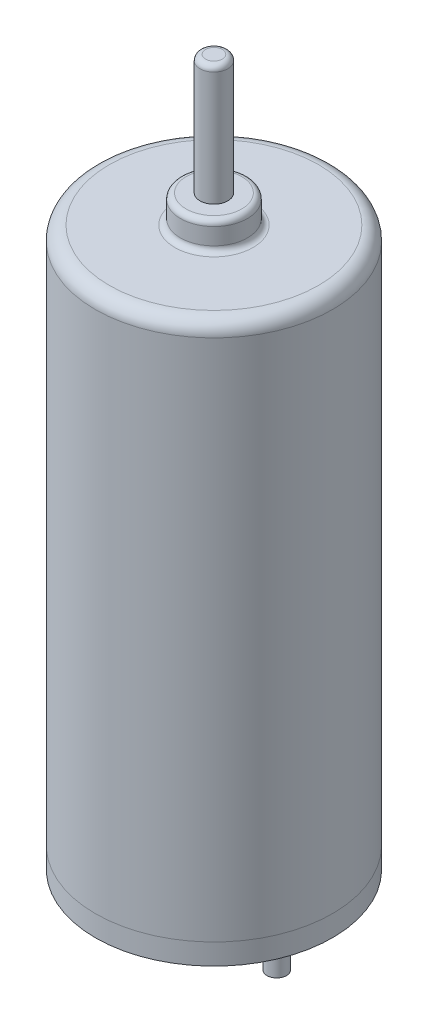
SolidWorks part; units mm, degrees
ref_plane "Front Plane" through (0, 0, 0) normal (0, 0, 1) x (1, 0, 0)
ref_plane "Top Plane" through (0, 0, 0) normal (0, 1, 0) x (1, 0, 0)
ref_plane "Right Plane" through (0, 0, 0) normal (1, 0, 0) x (0, 0, -1)
sketch "Sketch1" plane through (0, 0, 0) normal (0, 1, 0) x (1, 0, 0)
  circle A0 centre (0, 0) radius 4.25
  dimension "D1" = 8.5
extrude "Boss-Extrude1" add sketch "Sketch1" along normal blind 0.75
sketch "Sketch2" plane through (0, 0.75, 0) normal (0, 1, 0) x (1, 0, 0)
  circle A1 centre (0, 0) radius 4.25
  circle A2 centre (0, 0) radius 4.25
  dimension "D1" = 0
extrude "Boss-Extrude2" add sketch "Sketch2" along normal offset from surface (19.25 mm away) 20 separate body up to face at (0, 0, 4.25)
sketch "Sketch3" plane through (0, 20, 0) normal (0, 1, 0) x (1, 0, 0)
  circle A0 centre (0, 0) radius 1.2
  dimension "D1" = 2.4
extrude "Boss-Extrude3" add sketch "Sketch3" along normal blind 1
sketch "Sketch4" plane through (0, 21, 0) normal (0, 1, 0) x (1, 0, 0)
  circle A0 centre (0, 0) radius 0.5
  dimension "D1" = 1
extrude "Boss-Extrude4" add sketch "Sketch4" along normal blind 4.3
fillet "Fillet1" radius 0.5 1 edges at (0, 20, 4.25)
fillet "Fillet2" radius 0.2 3 edges at (0, 25.3, 0.5) (0, 21, 1.2) (0, 20, 1.2)
sketch "Sketch5" plane through (0, 0, 0) normal (0, -1, 0) x (1, 0, 0)
  line L0 (-4.25, 0) -> (4.25, 0) construction
  circle A0 centre (0, 0) radius 4.25 construction
  circle A1 centre (0, 0) radius 2.25
  circle A2 centre (-2.25, 0) radius 0.35
  circle A3 centre (2.25, 0) radius 0.35
  dimension "D1" = 4.5
  dimension "D2" = 0.7
extrude "Boss-Extrude5" add sketch "Sketch5" along normal blind 2 contours A2 | A3
